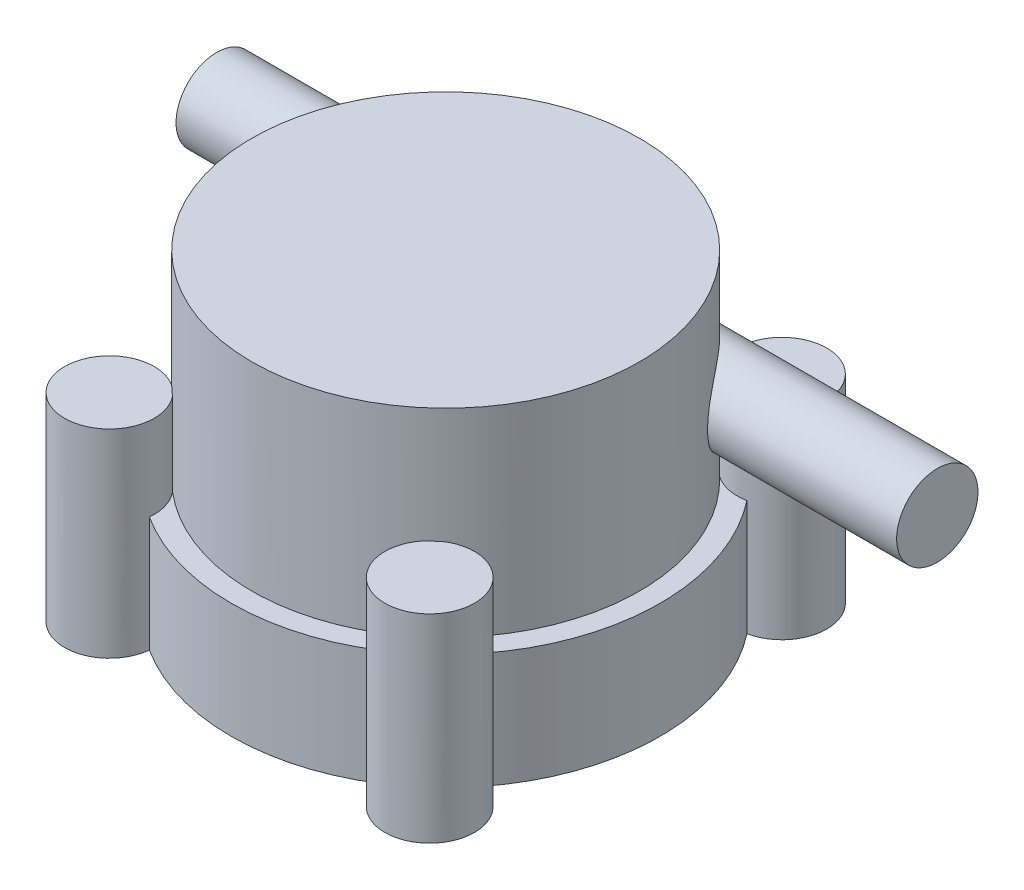
SolidWorks part; units mm, degrees
ref_plane "Front Plane" through (0, 0, 0) normal (0, 0, 1) x (1, 0, 0)
ref_plane "Top Plane" through (0, 0, 0) normal (0, 1, 0) x (1, 0, 0)
ref_plane "Right Plane" through (0, 0, 0) normal (1, 0, 0) x (0, 0, -1)
sketch "Sketch1" plane through (0, 0, 0) normal (0, 1, 0) x (1, 0, 0)
  circle A0 centre (0, 0) radius 16.75
  dimension "D1" = 33.5
extrude "Boss-Extrude1" add sketch "Sketch1" along normal blind 9
sketch "Sketch2" plane through (0, 9, 0) normal (0, 1, 0) x (1, 0, 0)
  circle A0 centre (0, 0) radius 15.125
  dimension "D1" = 30.25
extrude "Boss-Extrude2" add sketch "Sketch2" along normal blind 15.5
sketch "Sketch3" plane through (0, 0, 0) normal (0, -1, 0) x (1, 0, 0)
  line L0 (0, 0) -> (-16.75, 0) construction
  line L1 (0, 0) -> (0, 16.75) construction
  circle A0 centre (-12.5, 13.75) radius 3.5
  circle A1 centre (12.5, 13.75) radius 3.5
  circle A2 centre (0, 0) radius 16.75 construction
  circle A3 centre (12.5, -13.75) radius 3.5
  circle A4 centre (-12.5, -13.75) radius 3.5
  circle A5 centre (0, 0) radius 15.0826 construction
  dimension "D1" = 7
  dimension "D3" = 7
  dimension "D2" = 12.5
  dimension "D4" = 13.75
  dimension "D5" = 13.75
  dimension "D6" = 12.5
extrude "Boss-Extrude3" add sketch "Sketch3" against normal blind 15.5
ref_plane "Plane1" through (15.125, 0, 0) normal (1, 0, 0) x (0, 0, -1)
sketch "Sketch4" plane through (15.125, 0, 0) normal (1, 0, 0) x (0, 0, -1)
  circle A0 centre (10.25, 15.5) radius 3.175
  dimension "D1" = 6.35
extrude "Boss-Extrude4" add sketch "Sketch4" along normal blind 13 and the other way blind 15.5
mirror "Mirror1" about plane through (0, 0, 0) normal (1, 0, 0) of "Boss-Extrude4"
